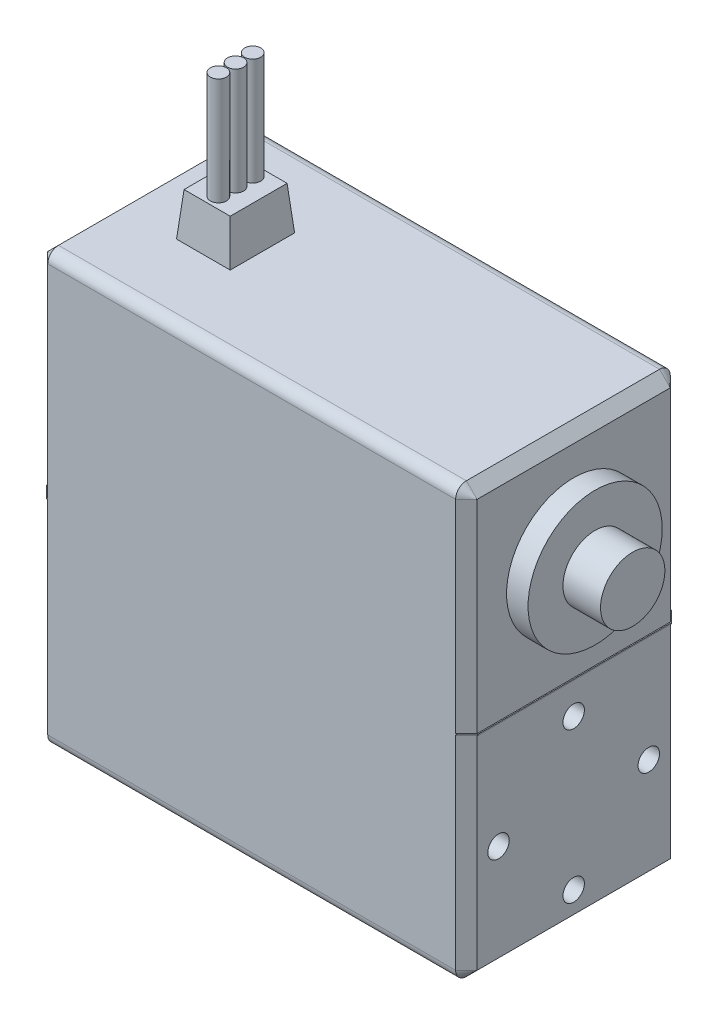
SolidWorks part; units mm, degrees
ref_plane "Спереди" through (0, 0, 0) normal (0, 0, 1) x (1, 0, 0)
ref_plane "Сверху" through (0, 0, 0) normal (0, 1, 0) x (1, 0, 0)
ref_plane "Справа" through (0, 0, 0) normal (1, 0, 0) x (0, 0, -1)
sketch "Sketch1" plane through (0, 0, 0) normal (0, 0, 1) x (1, 0, 0)
  line L0 (0, 0) -> (-20, 20) construction
  line L1 (20, 0) -> (20, 20)
  line L2 (20, 20) -> (-20, 20)
  line L3 (-20, 20) -> (-20, -20)
  line L4 (-20, -20) -> (20, -20)
  line L5 (20, -20) -> (20, 0)
  line L6 (0, 0) -> (20, -20) construction
  line L7 (0, 0) -> (20, 20) construction
  line L8 (0, 0) -> (-20, -20) construction
  dimension "D1" = 40
extrude "Основа" add sketch "Sketch1" along normal blind 20
sketch "Sketch2" plane through (20, 0, 0) normal (1, 0, 0) x (0, 0, -1)
  line L0 (-10, 10) -> (-10, 0) construction
  line L1 (-10, 0) -> (0, 0) construction
  line L2 (0, -20) -> (0, 20) construction
  circle A0 centre (-10, 10) radius 6.25
  dimension "D1" = 12.5
  dimension "D2" = 10
  dimension "D3" = 10
extrude "Выступы под ось" add sketch "Sketch2" along normal blind 2 and the other way blind 42
sketch "Sketch3" plane through (22, 0, 0) normal (1, 0, 0) x (0, 0, -1)
  circle A0 centre (-10, 10) radius 3
  dimension "D1" = 6
extrude "Ось" add sketch "Sketch3" along normal blind 3.5 and the other way blind 47.5
sketch "Sketch5" plane through (-20, 0, 0) normal (-1, 0, 0) x (0, 0, 1)
  line L0 (0, 0) -> (0, 0.1)
  line L1 (20, 20) -> (20, -20) construction
  line L2 (20, 0) -> (0, 0)
  line L3 (0, 20) -> (0, -20) construction
  line L4 (0, 0.1) -> (20, 0.1)
  line L5 (20, 0.1) -> (20, 0)
  dimension "D1" = 0.1
  dimension "D2" = 0.1
extrude "Рейка для выравнивания сборки" add sketch "Sketch5" along normal blind 0.1 and the other way blind 40.1
sketch "Sketch7" plane through (0, 0, 0) normal (0, 0, -1) x (-1, 0, 0)
  line L0 (0, 0) -> (-14, 0) construction
  text T0 "RDS315mg"
  dimension "D1" = 14
extrude "Модель сервы" cut sketch "Sketch7" against normal blind 0.3
fillet "Fillet1" radius 1 4 edges at (0, -20, 20) (0, -20, 0) (0, 20, 20) (0, 20, 0)
chamfer "Chamfer1" distance 1 angle 45 20 edges at (20, -19.7071, 0.2929) (20, -9.5, 0) (20, -20, 10) (20, -19.7071, 19.7071) (20, -9.5, 20) (20, 9.55, 0) (20, 19.7071, 0.2929) (20, 9.55, 20) (20, 19.7071, 19.7071) (20, 20, 10) (-20, -9.5, 20) (-20, -19.7071, 19.7071) (-20, -20, 10) (-20, -19.7071, 0.2929) (-20, -9.5, 0) (-20, 9.55, 20) (-20, 19.7071, 19.7071) (-20, 20, 10) (-20, 19.7071, 0.2929) (-20, 9.55, 0)
chamfer "Chamfer2" distance 1 angle 45 4 edges at (20.1, 0.05, 0) (20.1, 0.05, 20) (-20.1, 0.05, 20) (-20.1, 0.05, 0)
sketch "Эскиз1" plane through (20, 0, 0) normal (1, 0, 0) x (0, 0, -1)
  line L0 (-1, -20) -> (-19, -20) construction
  line L2 (-20, -19) -> (-20, 0) construction
  circle A0 centre (-10, -10) radius 7 construction
  circle A1 centre (-10, -10) radius 8 construction
  circle A2 centre (-10, -3) radius 1
  circle A3 centre (-3, -10) radius 1
  circle A4 centre (-10, -17) radius 1
  circle A5 centre (-17, -10) radius 1
  dimension "D1" = 14
  dimension "D2" = 16
  dimension "D3" = 10
  dimension "D4" = 10
extrude "Вырез-Вытянуть1" cut sketch "Эскиз1" against normal blind 2
sketch "Эскиз2" plane through (-20, 0, 0) normal (-1, 0, 0) x (0, 0, 1)
  line L0 (19, -20) -> (1, -20) construction
  line L1 (2.5, -17.5) -> (17.5, -17.5) construction
  line L2 (2.5, -17.5) -> (2.5, -2.5) construction
  line L3 (2.5, -2.5) -> (17.5, -2.5) construction
  line L4 (17.5, -17.5) -> (17.5, -2.5) construction
  line L5 (0, -19) -> (0, 0) construction
  line L6 (1, 0) -> (1, -19) construction
  line L7 (19, -19) -> (1, -19) construction
  line L8 (19, -19) -> (19, -1) construction
  line L10 (1, -19) -> (1, -2) construction
  circle A0 centre (2.5, -17.5) radius 1
  circle A1 centre (17.5, -17.5) radius 1
  circle A2 centre (17.5, -2.5) radius 1
  circle A3 centre (2.5, -2.5) radius 1
  dimension "D1" = 15
  dimension "D2" = 2.5
  dimension "D3" = 2.5
extrude "Вырез-Вытянуть2" cut sketch "Эскиз2" against normal blind 2
sketch "Sketch9" plane through (0, 20, 0) normal (0, 1, 0) x (1, 0, 0)
  line L0 (-20, -19) -> (-20, -1) construction
  line L1 (-14, -7) -> (-9, -7)
  line L2 (-14, -7) -> (-14, -13)
  line L3 (-14, -13) -> (-9, -13)
  line L4 (-9, -7) -> (-9, -13)
  line L5 (19, -10) -> (-19, -10) construction
  line L6 (19, -19) -> (19, -1) construction
  line L7 (-19, -1) -> (-19, -19) construction
  point P12 (19, -10)
  point P17 (-19, -10)
  point P18 (-9, -10)
  dimension "D1" = 5
  dimension "D2" = 6
  dimension "D3" = 6
extrude "провод" add sketch "Sketch9" along normal blind 4
sketch "Sketch10" plane through (0, 24, 0) normal (0, 1, 0) x (1, 0, 0)
  line L0 (-14, -13) -> (-9, -13) construction
  circle A0 centre (-11.5, -11.6) radius 0.75
  circle A1 centre (-11.5, -10) radius 0.75
  circle A2 centre (-11.5, -8.4) radius 0.75
  point P9 (-11.5, -13)
  dimension "D1" = 1.5
  dimension "D2" = 1.4
  dimension "D3" = 1.6
  dimension "D4" = 1.6
extrude "Extrude5" add sketch "Sketch10" along normal blind 10
chamfer "Chamfer3" distance 4 angle 5 4 edges at (-11.5, 24, 7) (-9, 24, 10) (-11.5, 24, 13) (-14, 24, 10) first distance on face at (-11.5, 22, 7) first distance on face at (-9, 22, 10) first distance on face at (-11.5, 22, 13) first distance on face at (-14, 22, 10)
